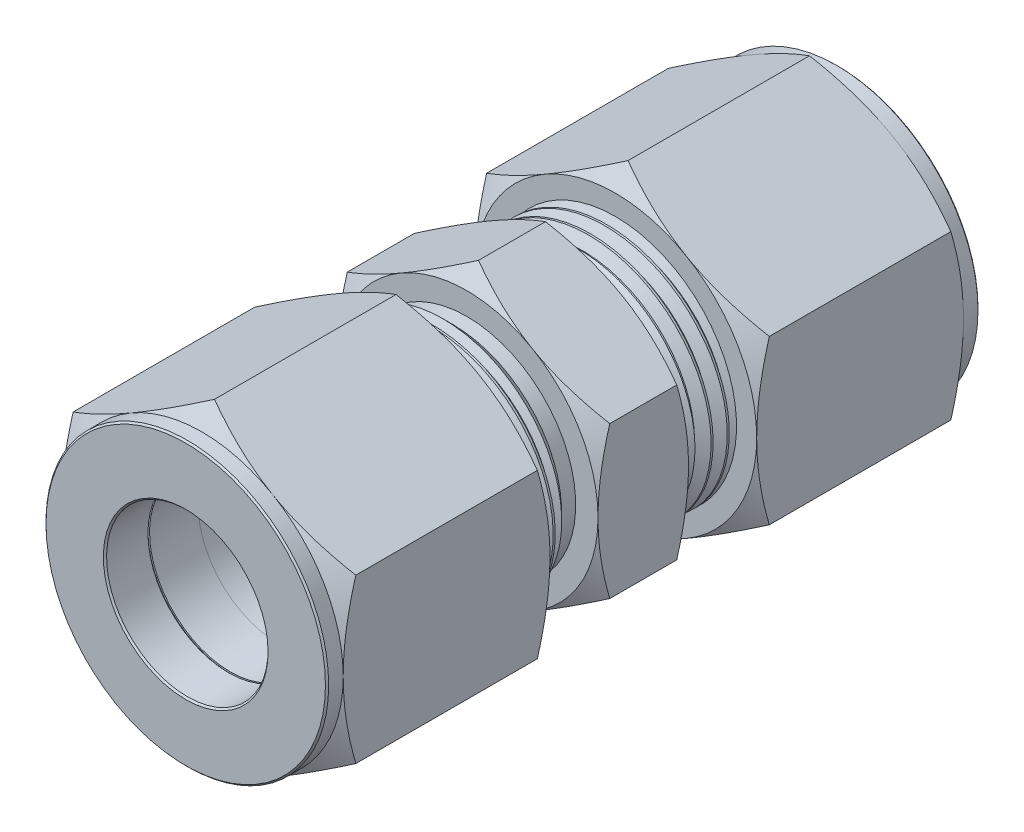
SolidWorks part; units mm, degrees
ref_plane "Front Plane" through (0, 0, 0) normal (0, 0, 1) x (1, 0, 0)
ref_plane "Top Plane" through (0, 0, 0) normal (0, 1, 0) x (1, 0, 0)
ref_plane "Right Plane" through (0, 0, 0) normal (1, 0, 0) x (0, 0, -1)
sketch "Sketch1" plane through (0, 0, 0) normal (1, 0, 0) x (0, 0, -1)
  line L0 (0, 0) -> (51.308, 0) construction
  line L1 (0, 6.35) -> (0, -6.35) construction
  line L2 (17.526, 11.1125) -> (17.526, -11.1125) construction
  line L3 (7.0104, 9.525) -> (7.0104, -9.525) construction
  line L4 (7.0104, 9.525) -> (7.0104, 8.255) construction
  line L5 (25.654, 10.3187) -> (25.654, -10.3187) construction
  line L6 (6.1976, 8.6614) -> (13.5128, 6.8834) construction
  line L7 (13.5128, 6.8834) -> (13.5128, 6.35) construction
  line L8 (13.5128, 6.35) -> (7.3152, 6.35) construction
  line L9 (7.3152, 6.35) -> (6.1976, 7.4676) construction
  line L10 (6.1976, 7.4676) -> (6.1976, 8.6614) construction
  line L11 (3.5052, 7.8359) -> (4.7752, 7.8359) construction
  line L12 (4.7752, 7.8359) -> (4.7752, 7.4676) construction
  line L13 (4.7752, 7.4676) -> (6.1976, 7.4676) construction
  line L14 (25.654, 5.1562) -> (25.654, -5.1562) construction
  line L15 (6.1976, 7.4676) -> (6.1976, 6.35) construction
  line L16 (7.3152, 6.35) -> (3.5052, 6.35) construction
  line L17 (3.5052, 6.35) -> (3.5052, 7.8359) construction
  line L18 (6.1976, 6.35) -> (7.3152, 6.35) construction
  line L19 (0, 6.35) -> (3.5052, 6.35) construction
  line L20 (3.5052, 6.35) -> (7.0104, 6.35) construction
  point P4 (1.778, 0)
  point P10 (7.0104, 0)
  point P12 (17.526, 0)
  point P15 (22.098, 0)
  point P16 (10.16, 0)
  point P17 (22.86, 0)
  point P33 (25.654, 0)
  dimension "BF OD 2" = 15.6718
  dimension "BF Lg" = 3.81
  dimension "BF Lg 1" = 1.27
  dimension "FF Lg" = 7.3152
  dimension "FF OD 1" = 13.7668
  dimension "FF OD 2" = 17.3228
  dimension "BF OD 1" = 14.9352
  dimension "Nut Lg" = 17.526
  dimension "Tube OD" = 12.7
  dimension "Nut Hex" = 22.225
  dimension "Straight Thread OD" = 19.05
  dimension "Nut Thread Lg" = 10.5156
  dimension "Straight Thread Pitch" = 1.27
  dimension "Lg 1" = 1.778
  dimension "Lg" = 51.308
  dimension "Body Hex" = 20.6375
  dimension "C" = 22.098
  dimension "D" = 30.988
  dimension "Insertion Depth" = 22.86
  dimension "E" = 10.3124
sketch "Sketch2" plane through (0, 0, 0) normal (0, 0, 1) x (1, 0, 0)
  line L0 (0, 6.35) -> (0, -6.35) construction
  line L1 (0, 12.8316) -> (-11.1125, 6.4158)
  line L2 (-11.1125, 6.4158) -> (-11.1125, -6.4158)
  line L3 (-11.1125, -6.4158) -> (0, -12.8316)
  line L4 (0, -12.8316) -> (11.1125, -6.4158)
  line L5 (11.1125, -6.4158) -> (11.1125, 6.4158)
  line L6 (11.1125, 6.4158) -> (0, 12.8316)
  line L7 (0, 12.8316) -> (0, 0) construction
  circle A0 centre (0, 0) radius 11.1125 construction
extrude "Boss-Extrude1" add sketch "Sketch2" against normal up to vertex (17.526 mm away) up to point (0, 0, -17.526)
sketch "Sketch3" plane through (0, 0, 0) normal (1, 0, 0) x (0, 0, -1)
  line L0 (0, 12.8316) -> (0, 11.1125)
  line L1 (0, 6.4158) -> (0, 12.8316) construction
  line L2 (0, 11.1125) -> (1.27, 11.1125)
  line L3 (1.27, 11.1125) -> (2.2625, 12.8316)
  line L4 (17.526, 12.8316) -> (0, 12.8316) construction
  line L5 (2.2625, 12.8316) -> (16.5335, 12.8316)
  line L6 (16.5335, 12.8316) -> (17.526, 11.1125)
  line L7 (17.526, 11.1125) -> (17.526, 12.8316)
  line L8 (17.526, 12.8316) -> (17.526, 14.5507)
  line L9 (17.526, 14.5507) -> (0, 14.5507)
  line L10 (0, 14.5507) -> (0, 12.8316)
  line L11 (0, 6.35) -> (0, 0)
  line L12 (0, 6.35) -> (0, -6.35) construction
  line L13 (0, 0) -> (17.526, 0)
  line L14 (17.526, 11.1125) -> (17.526, -11.1125) construction
  line L15 (17.526, 0) -> (17.526, 9.525)
  line L16 (17.526, 9.525) -> (7.0104, 9.525)
  line L17 (7.0104, 9.525) -> (7.0104, 8.255) construction
  line L18 (7.0104, 8.255) -> (3.5052, 8.255) construction
  line L19 (3.5052, 8.255) -> (3.5052, 6.35)
  line L20 (3.5052, 6.35) -> (0, 6.35)
  line L21 (3.5052, 8.255) -> (3.5052, 9.525) construction
  line L22 (3.5052, 9.525) -> (7.0104, 9.525) construction
  line L23 (7.0104, 8.89) -> (3.5052, 8.89)
  line L24 (3.5052, 8.89) -> (3.5052, 8.255)
  line L25 (7.0104, 8.89) -> (7.0104, 9.525)
  dimension "D1" = 30
  dimension "D2" = 1.27
revolve "Cut-Revolve1" cut sketch "Sketch3" angle 360 about L0
chamfer "Chamfer1" distance 0.127 angle 45 3 edges at (0, -6.35, -3.5052) (0, -6.35, 0) (11.1125, 0, 0)
sketch "Sketch4" plane through (0, 0, 0) normal (1, 0, 0) x (0, 0, -1)
  line L1 (25.654, 0) -> (10.16, 0)
  line L2 (25.654, 0) -> (25.654, 9.525)
  line L3 (25.654, 9.525) -> (10.16, 9.525)
  line L4 (10.16, 0) -> (10.16, 9.525)
  dimension "D1" = 15.494
revolve "Revolve1" add sketch "Sketch4" angle 360 about L1
sketch "Sketch5" plane through (0, 0, -10.16) normal (0, 0, -1) x (-1, 0, 0)
  circle A0 centre (0, 0) radius 9.525 construction
  circle A1 centre (0, 0) radius 9.525
  point P3 (0, 9.525)
curve "Helix/Spiral1" pitch 1.27 height 16.764 radius 9.525 centre (0, 0, -10.16) axis (0, 0, -1) start towards (0, 1, 0)
sketch "Sketch6" plane through (0, 0, 0) normal (1, 0, 0) x (0, 0, -1)
  line L0 (8.9694, 9.6625) -> (10.2394, 9.6625) construction
  line L1 (10.2394, 9.6625) -> (9.6044, 8.5626) construction
  line L2 (9.6044, 8.5626) -> (8.9694, 9.6625) construction
  line L3 (9.525, 8.7001) -> (9.6837, 8.7001) construction
  line L4 (9.0488, 9.525) -> (10.16, 9.525) construction
  line L5 (9.6044, 8.5626) -> (9.6044, 8.7001) construction
  line L6 (9.6044, 9.525) -> (9.6044, 9.6625) construction
  line L7 (9.525, 8.7001) -> (9.0091, 9.5937)
  line L8 (9.0091, 9.5937) -> (10.1997, 9.5937)
  line L9 (10.1997, 9.5937) -> (9.6837, 8.7001)
  line L10 (9.6837, 8.7001) -> (9.525, 8.7001)
  point P10 (9.6044, 9.5937)
  dimension "D1" = 1.27
  dimension "D2" = 0.1588
sweep "Cut-Sweep1" cut profiles "Sketch6" path "Helix/Spiral1" align with end faces yes
sketch "Sketch7" plane through (0, 0, -25.654) normal (0, 0, -1) x (-1, 0, 0)
  line L0 (0, 0) -> (0, 11.9151) construction
  line L1 (0, 11.9151) -> (-10.3188, 5.9575)
  line L2 (-10.3188, 5.9575) -> (-10.3188, -5.9575)
  line L3 (-10.3188, -5.9575) -> (0, -11.9151)
  line L4 (0, -11.9151) -> (10.3188, -5.9575)
  line L5 (10.3188, -5.9575) -> (10.3188, 5.9575)
  line L6 (10.3188, 5.9575) -> (0, 11.9151)
  circle A0 centre (0, 0) radius 10.3188 construction
extrude "Boss-Extrude2" add sketch "Sketch7" against normal up to vertex (3.556 mm away) up to point (0, 0, -22.098)
sketch "Sketch8" plane through (0, 0, 0) normal (1, 0, 0) x (0, 0, -1)
  line L0 (10.16, 9.6625) -> (10.16, 8.5626)
  line L1 (10.16, 8.5626) -> (11.2599, 9.6625)
  line L2 (11.2599, 9.6625) -> (10.16, 9.6625)
  line L3 (22.098, 9.6625) -> (19.8983, 9.6625)
  line L4 (19.8983, 9.6625) -> (20.9981, 8.5626)
  line L5 (20.9981, 8.5626) -> (22.098, 8.5626)
  line L6 (22.098, 8.5626) -> (22.098, 9.6625)
  line L7 (22.098, 10.3187) -> (23.0196, 11.9151)
  line L8 (22.098, 11.9151) -> (22.098, 5.9575) construction
  line L9 (22.098, 11.9151) -> (25.654, 11.9151) construction
  line L10 (23.0196, 11.9151) -> (25.654, 11.9151)
  line L11 (22.86, 5.1562) -> (25.654, 5.1562)
  line L13 (25.654, -5.9575) -> (25.654, 5.9575) construction
  line L14 (25.654, 11.9151) -> (25.654, 13.5114)
  line L15 (25.654, 13.5114) -> (22.098, 13.5114)
  line L16 (22.098, 13.5114) -> (22.098, 11.9151)
  line L17 (22.098, 11.9151) -> (22.098, 10.3187)
  line L18 (9.6044, 8.5626) -> (10.16, 8.5626) construction
  line L19 (10.2394, 9.6625) -> (10.16, 9.6625) construction
  line L20 (11.2599, 9.6625) -> (19.8983, 9.6625) construction
  line L21 (20.9981, 8.5626) -> (10.16, 8.5626) construction
  line L22 (10.16, 7.6983) -> (15.7074, 6.35)
  line L24 (10.16, 6.7352) -> (10.16, -8.7065) construction
  line L25 (6.1976, 8.6614) -> (13.5128, 6.8834) construction
  line L26 (25.654, 0) -> (10.16, 0)
  line L27 (10.16, 0) -> (10.16, 7.6983)
  line L28 (15.7074, 6.35) -> (22.86, 6.35)
  line L29 (22.86, 6.35) -> (22.86, 5.1562)
  line L30 (25.654, 5.1562) -> (25.654, 0)
  line L31 (22.86, 0) -> (22.86, 5.1562) construction
  line L32 (25.654, 10.3187) -> (25.654, -10.3187) construction
  dimension "D1" = 30
revolve "Cut-Revolve2" cut sketch "Sketch8" angle 360 about L0
sketch "Sketch9" plane through (0, 0, 0) normal (1, 0, 0) x (0, 0, -1)
  line L0 (6.1976, 8.6614) -> (6.1976, 7.4676)
  line L1 (6.1976, 7.4676) -> (7.3152, 6.35)
  line L2 (7.3152, 6.35) -> (13.5128, 6.35)
  line L3 (13.5128, 6.35) -> (13.5128, 6.8834)
  line L4 (13.5128, 6.8834) -> (6.1976, 8.6614)
revolve "Revolve2" add sketch "Sketch9" angle 360 about L0
sketch "Sketch10" plane through (0, 0, 0) normal (1, 0, 0) x (0, 0, -1)
  line L0 (3.5052, 7.8359) -> (4.7752, 7.8359)
  line L1 (4.7752, 7.8359) -> (4.7752, 7.4676)
  line L2 (4.7752, 7.4676) -> (6.1976, 7.4676)
  line L4 (6.1976, 7.4676) -> (7.3152, 6.35)
  line L5 (7.3152, 6.35) -> (3.5052, 6.35)
  line L6 (3.5052, 6.35) -> (3.5052, 7.8359)
revolve "Revolve3" add sketch "Sketch10" angle 360 about L0
ref_axis "Axis1" through (0, 0, -25.654) along (1, 0, 0)
pattern_circular "CirPattern1" count 2 over 360 about axis through (0, 0, -25.654) along (1, 0, 0) reverse direction yes of bodies 113 106 115 114
combine bodies "Combine1" operation type add bodies to combine 119 113
equation "\"D4@Helix/Spiral1\" = \"Straight Thread Pitch@Sketch1\""
equation "\"D3@Helix/Spiral1\" = \"D4@Helix/Spiral1\" + \"D1@Sketch4\""
equation "\"D1@Sketch6\" = \"D4@Helix/Spiral1\""
equation "\"D2@Sketch6\" = \"D1@Sketch6\" / 8"
